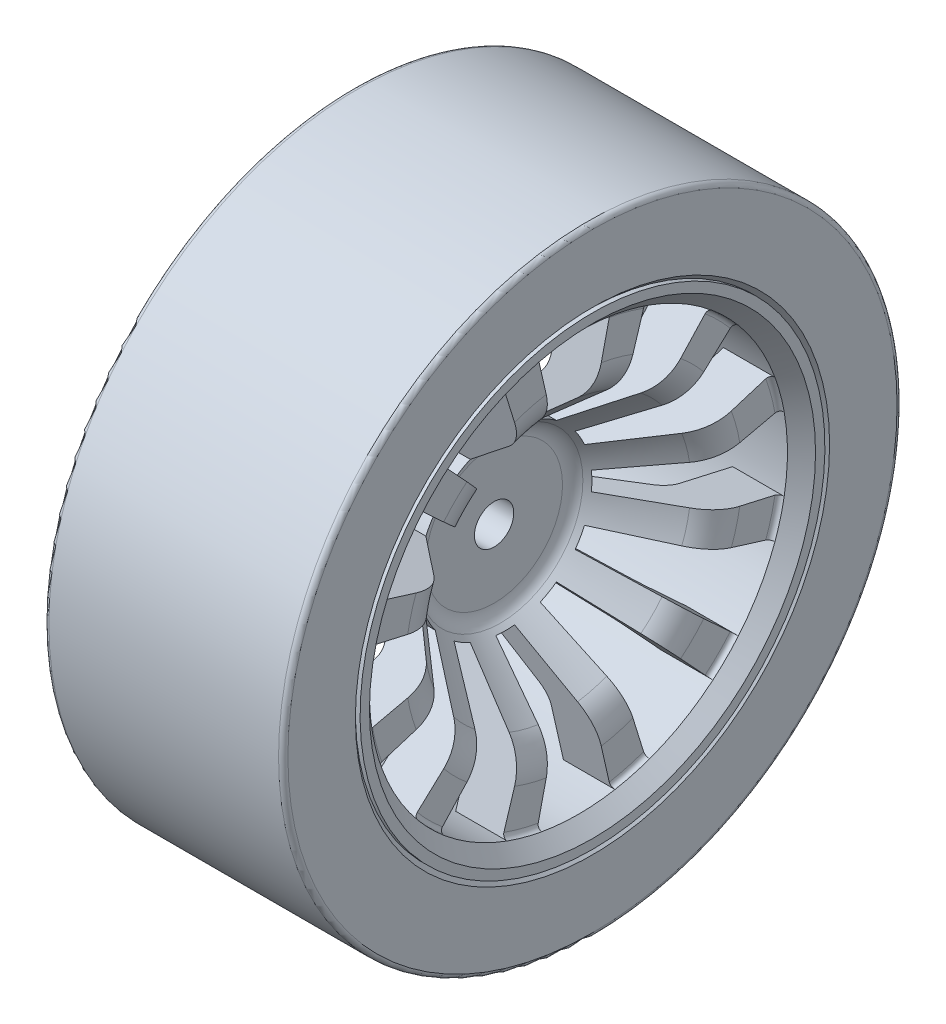
SolidWorks part; units mm, degrees
ref_plane "Plan de face" through (0, 0, 0) normal (0, 0, 1) x (1, 0, 0)
ref_plane "Plan de dessus" through (0, 0, 0) normal (0, 1, 0) x (1, 0, 0)
ref_plane "Plan de droite" through (0, 0, 0) normal (1, 0, 0) x (0, 0, -1)
sketch "Esquisse1" plane through (0, 0, 0) normal (0, 0, 1) x (1, 0, 0)
  line L0 (-5.25, 0) -> (-5.25, 8)
  line L1 (-5.25, 8) -> (-1.05, 8)
  line L2 (-1.05, 8) -> (-1.05, 8.5)
  line L3 (-1.05, 8.5) -> (5.75, 15.3)
  line L4 (5.75, 15.3) -> (5.75, 22.3)
  line L5 (5.75, 22.3) -> (-11.25, 22.3)
  line L6 (-11.25, 22.3) -> (-12.75, 23.8)
  line L7 (-12.75, 23.8) -> (-12.75, 24.8)
  line L8 (-12.75, 24.8) -> (12.75, 24.8)
  line L9 (12.75, 24.8) -> (12.75, 23.8)
  line L10 (10.75, 22.3) -> (11.25, 22.3)
  line L11 (10.75, 22.3) -> (10.75, 15.7)
  line L12 (10.75, 15.7) -> (2.25, 8.2)
  line L13 (2.25, 8.2) -> (2.25, 0)
  line L14 (2.25, 0) -> (-5.25, 0)
  line L15 (11.25, 22.3) -> (12.75, 23.8)
  line L16 (-5.25, 0) -> (13.948, 0) construction
  point P15 (0, 24.8)
  dimension "D1" = 25.5
  dimension "D2" = 2.5
  dimension "D3" = 1
  dimension "D4" = 22.3
  dimension "D5" = 18
  dimension "D6" = 15
  dimension "D7" = 45
  dimension "D8" = 45
  dimension "D9" = 8
  dimension "D10" = 8.2
  dimension "D11" = 6.6
  dimension "D12" = 0.5
  dimension "D13" = 4.2
  dimension "D14" = 0.5
  dimension "D15" = 18.5
revolve "Révolution1" add sketch "Esquisse1" angle 360 about L16
fillet "Congé1" radius 5 1 edges at (10.75, -15.7, 0)
sketch "Esquisse2" plane through (2.25, 0, 0) normal (1, 0, 0) x (0, 0, -1)
  circle A0 centre (0, 0) radius 2.1
  dimension "D1" = 4.2
extrude "Enlèv. mat.-Extru.1" cut sketch "Esquisse2" against normal through all
fillet "Congé2" radius 2 1 edges at (2.25, -8.2, 0)
sketch "Esquisse3" plane through (-5.25, 0, 0) normal (-1, 0, 0) x (0, 0, 1)
  line L1 (6.9282, 0) -> (3.4641, 6)
  line L2 (3.4641, 6) -> (-3.4641, 6)
  line L3 (-3.4641, 6) -> (-6.9282, 0)
  line L4 (-6.9282, 0) -> (-3.4641, -6)
  line L5 (-3.4641, -6) -> (3.4641, -6)
  line L6 (3.4641, -6) -> (6.9282, 0)
  circle A0 centre (0, 0) radius 6 construction
  dimension "D1" = 12
extrude "Enlèv. mat.-Extru.2" cut sketch "Esquisse3" against normal blind 4.5
fillet "Congé3" radius 3 2 edges at (5.75, -15.3, 0) (-1.05, -8.5, 0)
sketch "Esquisse4" plane through (-5.25, 0, 0) normal (-1, 0, 0) x (0, 0, 1)
  line L0 (9.1949, 1) -> (21.9563, 3.9)
  line L1 (21.9563, -3.9) -> (9.1949, -1)
  line L2 (8.463, -3.7314) -> (20.9647, -7.6007)
  line L3 (17.0647, -14.3557) -> (7.463, -5.4635)
  line L4 (5.4635, -7.463) -> (14.3557, -17.0647)
  line L5 (7.6007, -20.9647) -> (3.7314, -8.463)
  line L6 (1, -9.1949) -> (3.9, -21.9563)
  line L7 (-3.9, -21.9563) -> (-1, -9.1949)
  line L8 (-3.7314, -8.463) -> (-7.6007, -20.9647)
  line L9 (-14.3557, -17.0647) -> (-5.4635, -7.463)
  line L10 (-7.463, -5.4635) -> (-17.0647, -14.3557)
  line L11 (-20.9647, -7.6007) -> (-8.463, -3.7314)
  line L12 (-9.1949, -1) -> (-21.9563, -3.9)
  line L13 (-21.9563, 3.9) -> (-9.1949, 1)
  line L14 (-8.463, 3.7314) -> (-20.9647, 7.6007)
  line L15 (-17.0647, 14.3557) -> (-7.463, 5.4635)
  line L16 (-5.4635, 7.463) -> (-14.3557, 17.0647)
  line L17 (-7.6007, 20.9647) -> (-3.7314, 8.463)
  line L18 (-1, 9.1949) -> (-3.9, 21.9563)
  line L19 (3.9, 21.9563) -> (1, 9.1949)
  line L20 (3.7314, 8.463) -> (7.6007, 20.9647)
  line L21 (14.3557, 17.0647) -> (5.4635, 7.463)
  line L22 (7.463, 5.4635) -> (17.0647, 14.3557)
  line L23 (20.9647, 7.6007) -> (8.463, 3.7314)
  circle A0 centre (0, 0) radius 22.3 construction
  arc A1 (21.9563, -3.9) -> (21.9563, 3.9) centre (0, 0) ccw
  circle A2 centre (0, 0) radius 9.2491 construction
  arc A3 (9.1949, 1) -> (9.1949, -1) centre (0, 0) cw
  arc A4 (17.0647, -14.3557) -> (20.9647, -7.6007) centre (0, 0) ccw
  arc A5 (8.463, -3.7314) -> (7.463, -5.4635) centre (0, 0) cw
  arc A6 (7.6007, -20.9647) -> (14.3557, -17.0647) centre (0, 0) ccw
  arc A7 (5.4635, -7.463) -> (3.7314, -8.463) centre (0, 0) cw
  arc A8 (-3.9, -21.9563) -> (3.9, -21.9563) centre (0, 0) ccw
  arc A9 (1, -9.1949) -> (-1, -9.1949) centre (0, 0) cw
  arc A10 (-14.3557, -17.0647) -> (-7.6007, -20.9647) centre (0, 0) ccw
  arc A11 (-3.7314, -8.463) -> (-5.4635, -7.463) centre (0, 0) cw
  arc A12 (-20.9647, -7.6007) -> (-17.0647, -14.3557) centre (0, 0) ccw
  arc A13 (-7.463, -5.4635) -> (-8.463, -3.7314) centre (0, 0) cw
  arc A14 (-21.9563, 3.9) -> (-21.9563, -3.9) centre (0, 0) ccw
  arc A15 (-9.1949, -1) -> (-9.1949, 1) centre (0, 0) cw
  arc A16 (-17.0647, 14.3557) -> (-20.9647, 7.6007) centre (0, 0) ccw
  arc A17 (-8.463, 3.7314) -> (-7.463, 5.4635) centre (0, 0) cw
  arc A18 (-7.6007, 20.9647) -> (-14.3557, 17.0647) centre (0, 0) ccw
  arc A19 (-5.4635, 7.463) -> (-3.7314, 8.463) centre (0, 0) cw
  arc A20 (3.9, 21.9563) -> (-3.9, 21.9563) centre (0, 0) ccw
  arc A21 (-1, 9.1949) -> (1, 9.1949) centre (0, 0) cw
  arc A22 (14.3557, 17.0647) -> (7.6007, 20.9647) centre (0, 0) ccw
  arc A23 (3.7314, 8.463) -> (5.4635, 7.463) centre (0, 0) cw
  arc A24 (20.9647, 7.6007) -> (17.0647, 14.3557) centre (0, 0) ccw
  arc A25 (7.463, 5.4635) -> (8.463, 3.7314) centre (0, 0) cw
  point P2 (9.2491, 0)
  point P10 (22.3, 0)
  point P58 (0, 0)
  dimension "D1" = 7.8
  dimension "D2" = 2
  dimension "D3" = 12
extrude "Enlèv. mat.-Extru.3" cut sketch "Esquisse4" against normal through all
fillet "Congé4" radius 0.5 12 edges at (10.75, -21.5401, 5.7717) (10.75, -21.5401, -5.7717) (10.75, -15.7685, 15.7685) (10.75, -5.7717, 21.5401) (10.75, 5.7717, 21.5401) (10.75, 15.7685, 15.7685) (10.75, 21.5401, 5.7717) (10.75, 21.5401, -5.7717) (10.75, 15.7685, -15.7685) (10.75, 5.7717, -21.5401) (10.75, -15.7685, -15.7685) (10.75, -5.7717, -21.5401)
sketch "Esquisse5" plane through (0, 0, 0) normal (0, 1, 0) x (1, 0, 0)
  line L0 (12.75, -24.8) -> (12.75, 24.8) construction
  line L1 (-12.25, 24.8) -> (12.25, 24.8)
  line L2 (-12.75, 25.3) -> (-12.75, 33)
  line L3 (-12.75, 33) -> (12.75, 33)
  line L4 (12.75, 25.3) -> (12.75, 33)
  line L5 (-12.75, 0) -> (12.75, 0) construction
  line L6 (-12.75, 24.8) -> (-12.75, -24.8) construction
  line L7 (12.75, -23.8) -> (12.75, 23.8) construction
  line L8 (-12.25, 24.8) -> (-12.75, 25.3)
  line L9 (12.25, 24.8) -> (12.75, 25.3)
  point P0 (-12.75, 24.8)
  point P3 (12.75, 24.8)
  dimension "D1" = 33
revolve "Révolution2" add sketch "Esquisse5" angle 360 about L5
fillet "Congé5" radius 0.5 2 edges at (-12.75, 0, 33) (12.75, 0, 33)
